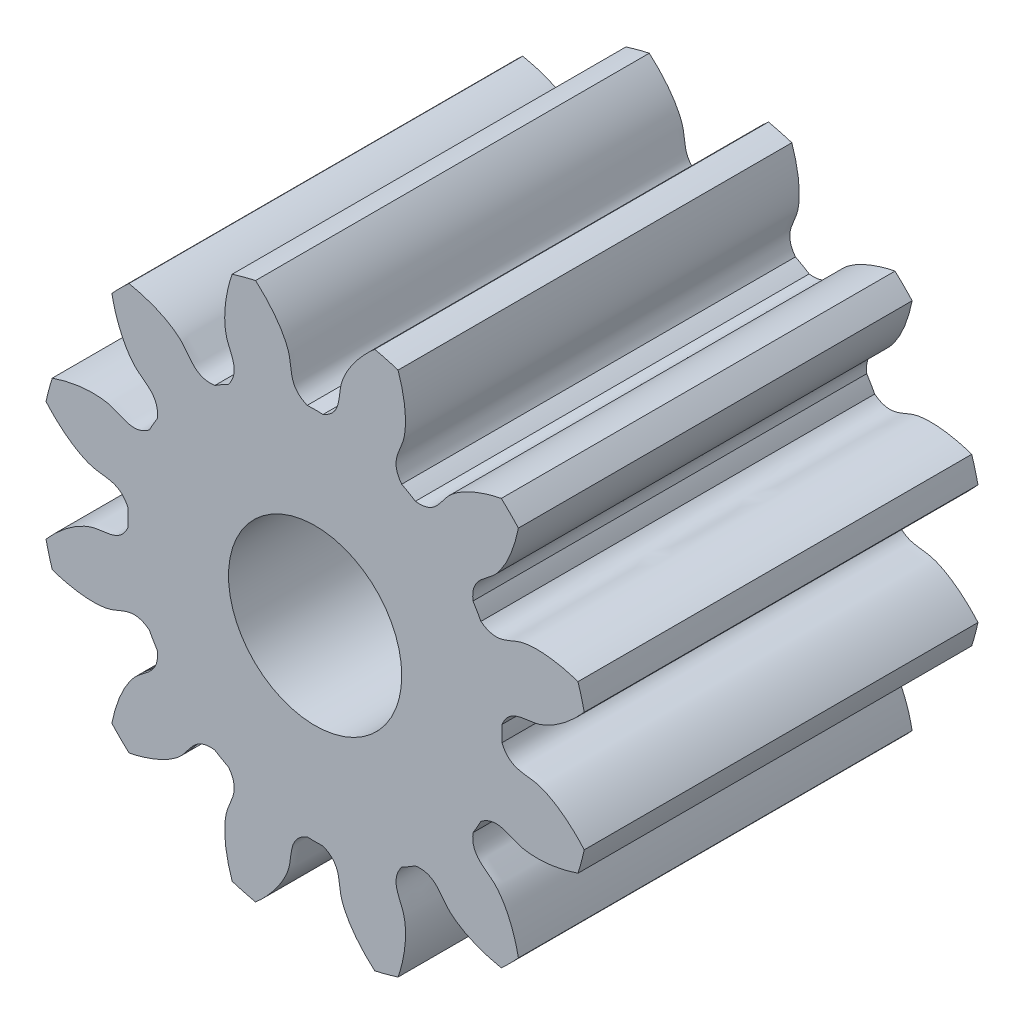
SolidWorks part; units mm, degrees
ref_plane "前视基准面" through (0, 0, 0) normal (0, 0, 1) x (1, 0, 0)
ref_plane "上视基准面" through (0, 0, 0) normal (0, 1, 0) x (1, 0, 0)
ref_plane "右视基准面" through (0, 0, 0) normal (1, 0, 0) x (0, 0, -1)
other "Configuration Table"
sketch "草图1" plane through (0, 0, 0) normal (0, 0, 1) x (1, 0, 0)
  circle A0 centre (0, 0) radius 3.5
extrude "凸台-拉伸1" add sketch "草图1" along normal blind 5
ref_axis "基准轴1" through (0, 0, 5) along (0, 0, -1)
sketch "草图2" plane through (0, 0, 0) normal (0, 0, 1) x (1, 0, 0)
  line L0 (0, 0) -> (0, 3.5) construction
  circle A0 centre (0, 0) radius 3.5 construction
  arc A1 (0.1004, 2.3729) -> (-0.1004, 2.3729) centre (0, 0) ccw
  arc A2 (1.7488, 3.9475) -> (-1.7488, 3.9475) centre (0, 0) ccw
  spline S0 degree 3 poles (0.1004, 2.3729) (0.3404, 2.4747) (0.2872, 2.6724) (0.3381, 2.8447) (0.3413, 2.855) (0.3451, 2.8662) (0.3495, 2.8784) (0.3546, 2.8915) (0.3603, 2.9056) (0.3668, 2.9206) (0.374, 2.9366) (0.3821, 2.9533) (0.3909, 2.971) (0.4007, 2.9894) (0.4114, 3.0086) (0.423, 3.0286) (0.4356, 3.0493) (0.4492, 3.0707) (0.4639, 3.0928) (0.4796, 3.1155) (0.4965, 3.1388) (0.5145, 3.1626) (0.5337, 3.187) (0.554, 3.2119) (0.5756, 3.2372) (0.5985, 3.2629) (0.6226, 3.289) (0.648, 3.3154) (0.6748, 3.342) (0.7028, 3.369) (0.7323, 3.3961) (0.7631, 3.4234) (0.7954, 3.4507) (0.829, 3.4782) (0.8641, 3.5057) (0.9006, 3.5331) (0.9385, 3.5604) (0.978, 3.5877) (1.0189, 3.6147) (1.0613, 3.6416) (1.1052, 3.6681) (1.1506, 3.6944) (1.1975, 3.7203) (1.2459, 3.7457) (1.2958, 3.7707) (1.3472, 3.7952) (1.4001, 3.8191) (1.4546, 3.8424) (1.5105, 3.865) (1.5679, 3.8869) (1.6472, 3.9154) (1.7078, 3.9351) (1.7488, 3.9475) knots 0 0 0 0 0.218015 0.222044 0.226546 0.231522 0.236972 0.242897 0.249295 0.256167 0.263513 0.271332 0.279626 0.288394 0.297636 0.307351 0.317541 0.328204 0.339341 0.350953 0.363038 0.375597 0.38863 0.402137 0.416118 0.430573 0.445502 0.460904 0.476781 0.493132 0.509956 0.527255 0.545027 0.563273 0.581994 0.601188 0.620856 0.640998 0.661614 0.682704 0.704268 0.726305 0.748817 0.771803 0.795262 0.819196 0.843603 0.868484 0.89384 0.919669 0.945972 1 1 1 1
  spline S1 degree 3 poles (-0.1004, 2.3729) (-0.3404, 2.4747) (-0.2872, 2.6724) (-0.3381, 2.8447) (-0.3413, 2.855) (-0.3451, 2.8662) (-0.3495, 2.8784) (-0.3546, 2.8915) (-0.3603, 2.9056) (-0.3668, 2.9206) (-0.374, 2.9366) (-0.3821, 2.9533) (-0.3909, 2.971) (-0.4007, 2.9894) (-0.4114, 3.0086) (-0.423, 3.0286) (-0.4356, 3.0493) (-0.4492, 3.0707) (-0.4639, 3.0928) (-0.4796, 3.1155) (-0.4965, 3.1388) (-0.5145, 3.1626) (-0.5337, 3.187) (-0.554, 3.2119) (-0.5756, 3.2372) (-0.5985, 3.2629) (-0.6226, 3.289) (-0.648, 3.3154) (-0.6748, 3.342) (-0.7028, 3.369) (-0.7323, 3.3961) (-0.7631, 3.4234) (-0.7954, 3.4507) (-0.829, 3.4782) (-0.8641, 3.5057) (-0.9006, 3.5331) (-0.9385, 3.5604) (-0.978, 3.5877) (-1.0189, 3.6147) (-1.0613, 3.6416) (-1.1052, 3.6681) (-1.1506, 3.6944) (-1.1975, 3.7203) (-1.2459, 3.7457) (-1.2958, 3.7707) (-1.3472, 3.7952) (-1.4001, 3.8191) (-1.4546, 3.8424) (-1.5105, 3.865) (-1.5679, 3.8869) (-1.6472, 3.9154) (-1.7078, 3.9351) (-1.7488, 3.9475) knots 0 0 0 0 0.218015 0.222044 0.226546 0.231522 0.236972 0.242897 0.249295 0.256167 0.263513 0.271332 0.279626 0.288394 0.297636 0.307351 0.317541 0.328204 0.339341 0.350953 0.363038 0.375597 0.38863 0.402137 0.416118 0.430573 0.445502 0.460904 0.476781 0.493132 0.509956 0.527255 0.545027 0.563273 0.581994 0.601188 0.620856 0.640998 0.661614 0.682704 0.704268 0.726305 0.748817 0.771803 0.795262 0.819196 0.843603 0.868484 0.89384 0.919669 0.945972 1 1 1 1
extrude "切除-拉伸1" cut sketch "草图2" along normal through all
pattern_circular "阵列(圆周)1" count 12 over 360 about axis through (0, 0, 5) along (0, 0, -1) of "切除-拉伸1"
sketch "草图3" plane through (0, 0, 0) normal (0, 0, 1) x (1, 0, 0)
  circle A0 centre (0, 0) radius 3 construction
  dimension "Dn" = 6
sketch "草图4" plane through (0, 0, 5) normal (0, 0, 1) x (1, 0, 0)
  circle A0 centre (0, 0) radius 1.1
  dimension "D1" = 2.2
extrude "切除-拉伸2" cut sketch "草图4" against normal up to next
